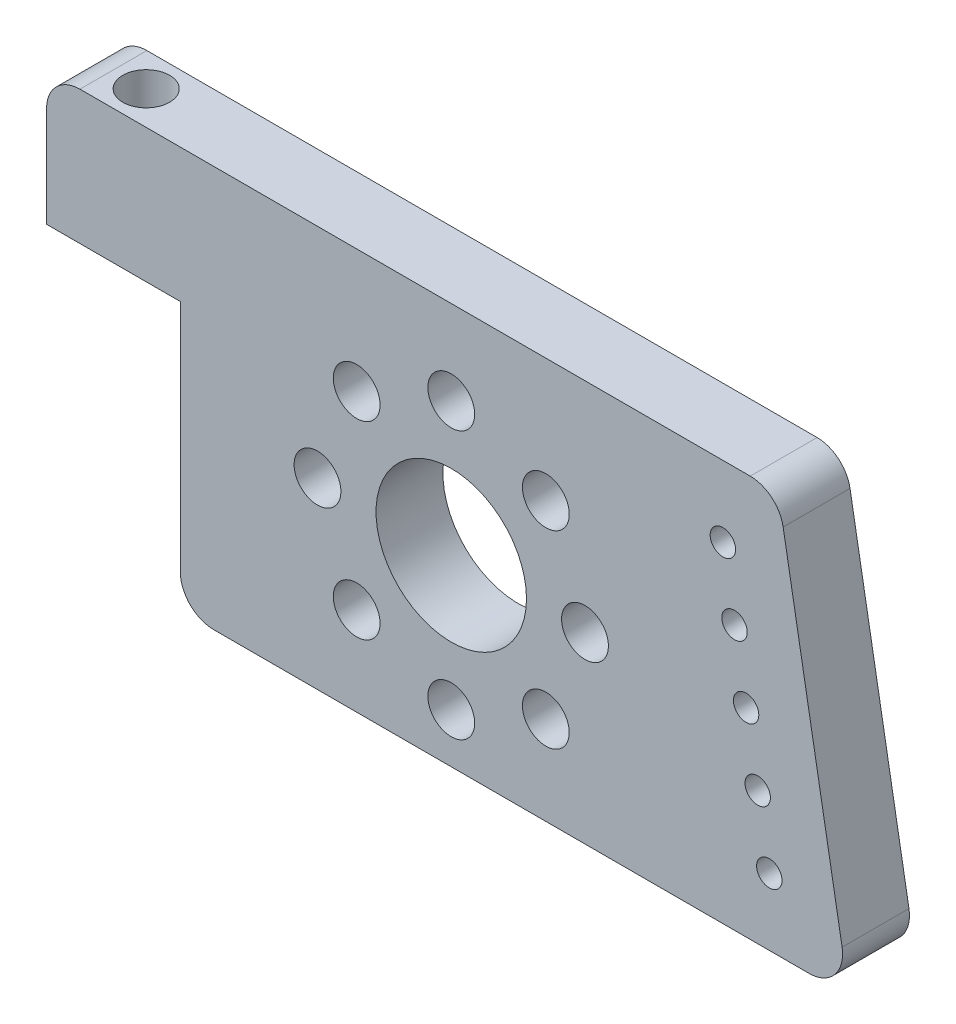
SolidWorks part; units mm, degrees
note: The reader was unsure of these and kept them because the rebuilt part matched: shared geometry of "Sketch3<3>".
ref_plane "Front Plane" through (0, 0, 0) normal (0, 0, 1) x (1, 0, 0)
ref_plane "Top Plane" through (0, 0, 0) normal (0, 1, 0) x (1, 0, 0)
ref_plane "Right Plane" through (0, 0, 0) normal (1, 0, 0) x (0, 0, -1)
sketch "Sketch1" plane through (0, 0, 0) normal (0, 0, 1) x (1, 0, 0)
  line L1 (-63.5, -42.6077) -> (63.5, -42.6077)
  line L2 (-63.5, -42.6077) -> (-63.5, 8.1923)
  line L3 (-50.0639, 33.5923) -> (50.0639, 33.5923)
  line L4 (63.5, -42.6077) -> (50.0639, 33.5923)
  line L5 (-63.5, -42.6077) -> (50.0639, 33.5923) construction
  line L6 (-50.0639, 33.5923) -> (63.5, -42.6077) construction
  line L7 (-63.5, -42.6077) -> (-88.9, -42.6077) construction
  line L8 (-63.5, -42.6077) -> (-63.5, 8.1923) construction
  line L9 (-63.5, 8.1923) -> (-88.9, 8.1923)
  line L10 (-88.9, -42.6077) -> (-88.9, 8.1923) construction
  line L11 (-12.0425, -7.8157) -> (6.7181, -4.5077) construction
  line L13 (-50.0639, 33.5923) -> (-88.9, 33.5923)
  line L14 (-88.9, 33.5923) -> (-88.9, 8.1923)
  circle A0 centre (-12.0425, -7.8157) radius 14.2875
  point P0 (0, 0)
  dimension "D3" = 25.4
  dimension "D5" = 28.575
  dimension "D1" = 127
  dimension "D2" = 76.2
  dimension "D4" = 50.8
  dimension "D6" = 19.05
  dimension "D7" = 10
  dimension "D8" = 80
extrude "Boss-Extrude1" add sketch "Sketch1" along normal blind 12.7
sketch "Sketch2" plane through (0, 0, 12.7) normal (0, 0, 1) x (1, 0, 0)
  circle A0 centre (-12.0425, -7.8157) radius 25.4 construction
  circle A3 centre (-12.0425, -33.2157) radius 2.413
  dimension "D1" = 4.826
  dimension "D3" = 50.8
extrude "Initial Mounting" cut sketch "Sketch2" against normal through all
pattern_circular "Mounting Pattern" count 8 over 360 about axis through (-12.0425, -7.8157, 0) along (0, 0, 1) of "Initial Mounting"
fillet "Fillet1" radius 6.35 4 edges at (-63.5, -42.6077, 6.35) (63.5, -42.6077, 6.35) (50.0639, 33.5923, 6.35) (-88.9, 33.5923, 6.35)
sketch "Sketch3" plane through (0, 8.1923, 0) normal (0, -1, 0) x (1, 0, 0)
  line L0 (-63.5, 6.35) -> (-76.327, 6.35) construction
  line L1 (-63.5, 12.7) -> (-63.5, 0) construction
  circle A0 centre (-76.327, 6.35) radius 2.413
  circle A1 centre (-76.327, 6.35) radius 4.445
  dimension "D1" = 8.89
  dimension "D2" = 4.826
  dimension "D3" = 12.827
extrude "Cut-Extrude1" cut sketch "Sketch3" against normal through all contours A0
extrude "Cut-Extrude2" cut sketch "Sketch3<3>" against normal through all from offset 12.7
sketch "Sketch3<3>" plane through (0, 8.1923, 0) normal (0, -1, 0) x (1, 0, 0) same geometry as "Sketch3"
sketch "Sketch4" plane through (0, 0, 12.7) normal (0, 0, 1) x (1, 0, 0)
  circle A2 centre (48.3647, -29.9077) radius 2.413
  circle A7 centre (48.3647, -29.9077) radius 2.413 construction
  dimension "D1" = 4.826
extrude "Cut-Extrude3" cut sketch "Sketch4" against normal through all
pattern_linear "LPattern1" count 5 spacing 12.7 along (-0.1736, 0.9848, 0) of "Cut-Extrude3"
sketch "Sketch5" plane through (0, 0, 0) normal (0, 0, -1) x (-1, 0, 0)
  circle A0 centre (12.0425, 17.5843) radius 4.445
  dimension "D1" = 8.89
extrude "Cut-Extrude4" cut sketch "Sketch5" along normal blind 6.35 from surface at -12.7 starting at face at (48.5724, -17.4007, 12.7)
pattern_circular "CirPattern1" count 8 over 360 about axis through (-12.0425, -7.8157, 0) along (0, 0, 1) of "Cut-Extrude4"
